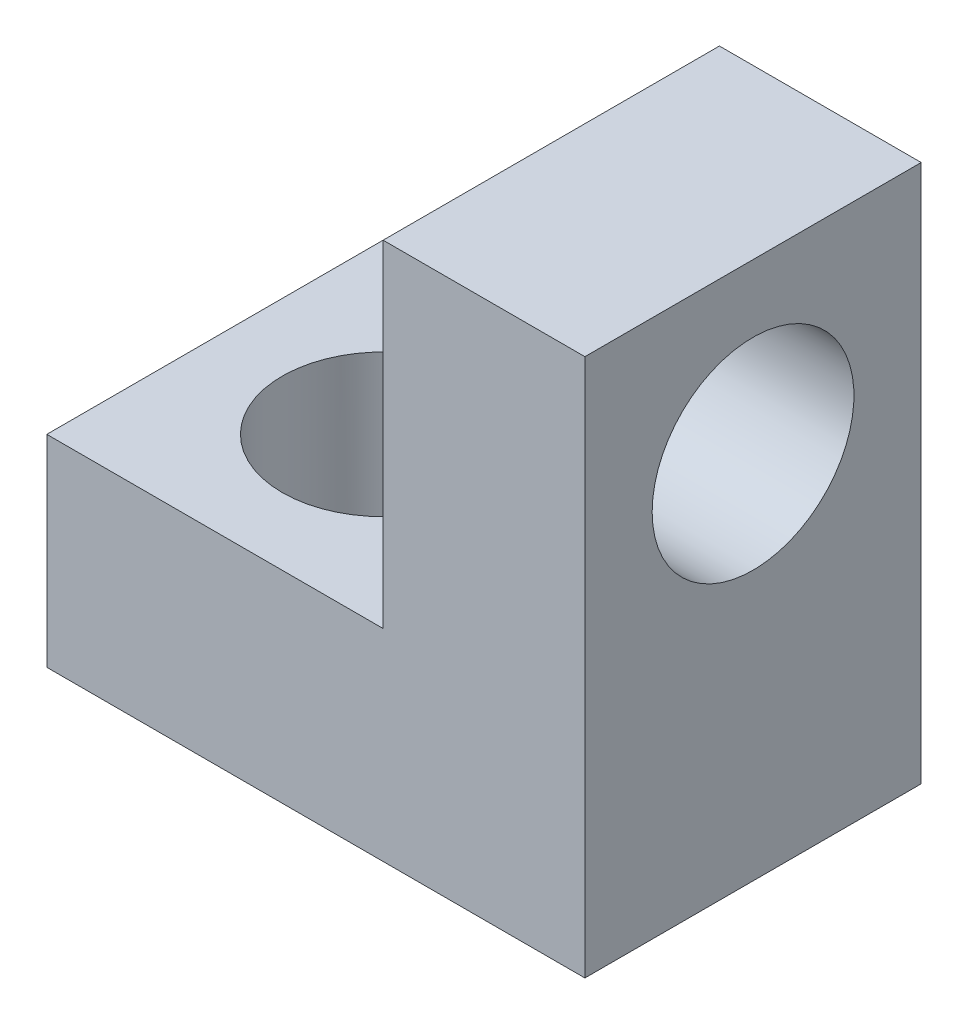
SolidWorks part; units mm, degrees
ref_plane "Front Plane" through (0, 0, 0) normal (0, 0, 1) x (1, 0, 0)
ref_plane "Top Plane" through (0, 0, 0) normal (0, 1, 0) x (1, 0, 0)
ref_plane "Right Plane" through (0, 0, 0) normal (1, 0, 0) x (0, 0, -1)
sketch "Sketch1" plane through (0, 0, 0) normal (0, 1, 0) x (1, 0, 0)
  line L1 (-4, -2.5) -> (4, -2.5)
  line L2 (-4, -2.5) -> (-4, 2.5)
  line L3 (-4, 2.5) -> (4, 2.5)
  line L4 (4, -2.5) -> (4, 2.5)
  line L5 (-4, -2.5) -> (4, 2.5) construction
  line L6 (-4, 2.5) -> (4, -2.5) construction
  point P0 (0, 0)
  dimension "D1" = 8
  dimension "D2" = 5
extrude "Boss-Extrude1" add sketch "Sketch1" along normal blind 3
sketch "Sketch2" plane through (0, 3, 0) normal (0, 1, 0) x (1, 0, 0)
  line L0 (-4, -2.5) -> (4, -2.5) construction
  line L1 (4, 2.5) -> (1, 2.5)
  line L2 (4, 2.5) -> (4, -2.5)
  line L3 (4, -2.5) -> (1, -2.5)
  line L4 (1, 2.5) -> (1, -2.5)
  dimension "D1" = 3
extrude "Boss-Extrude2" add sketch "Sketch2" along normal blind 5
sketch "Sketch3" plane through (0, 3, 0) normal (0, 1, 0) x (1, 0, 0)
  line L0 (1, 2.5) -> (-4, 2.5) construction
  line L1 (-4, 2.5) -> (-4, -2.5) construction
  circle A0 centre (-1.5, 0) radius 1.5
  dimension "D3" = 3
  dimension "D1" = 2.5
  dimension "D2" = 2.5
extrude "Cut-Extrude1" cut sketch "Sketch3" against normal blind 5
sketch "Sketch4" plane through (1, 0, 0) normal (-1, 0, 0) x (0, 0, 1)
  line L0 (2.5, 8) -> (2.5, 3) construction
  line L1 (-2.5, 3) -> (2.5, 3) construction
  circle A0 centre (0, 5.5) radius 1.5
  point P6 (1.2678, 4.6656)
  dimension "D3" = 3
  dimension "D1" = 2.5
  dimension "D2" = 2.5
extrude "Cut-Extrude2" cut sketch "Sketch4" against normal blind 5
